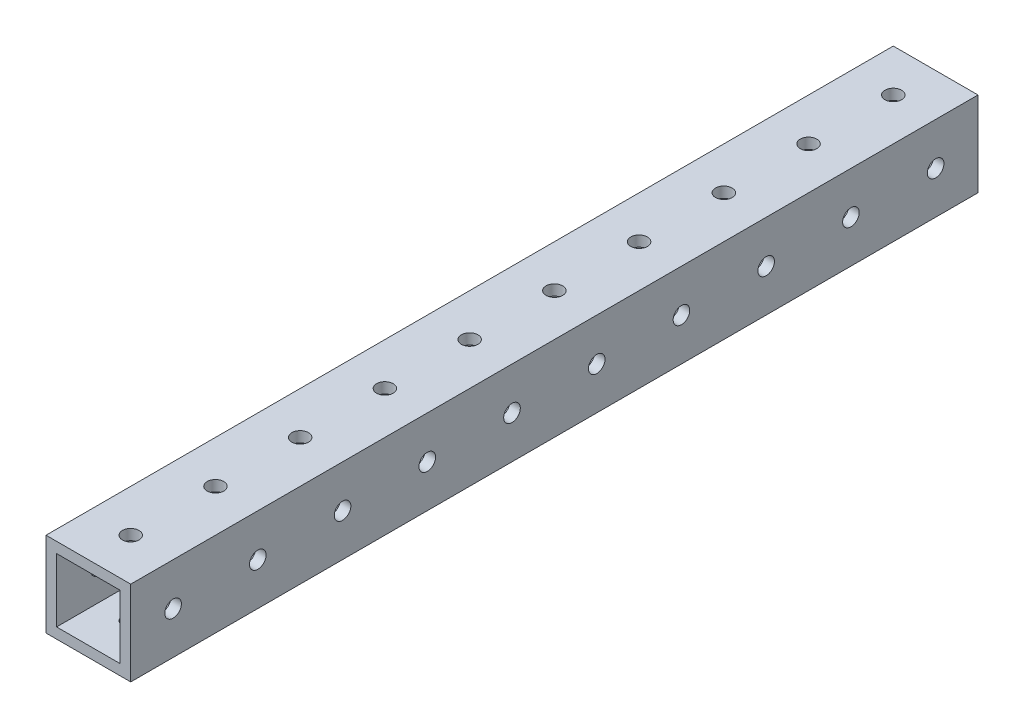
SolidWorks part; units mm, degrees
material "6061-T6 (SS)"
ref_plane "Front Plane" through (0, 0, 0) normal (0, 0, 1) x (1, 0, 0)
ref_plane "Top Plane" through (0, 0, 0) normal (0, 1, 0) x (1, 0, 0)
ref_plane "Right Plane" through (0, 0, 0) normal (1, 0, 0) x (0, 0, -1)
sketch "Sketch1" plane through (0, 0, 0) normal (0, 0, 1) x (1, 0, 0)
  line L1 (-12.7, -12.7) -> (12.7, -12.7)
  line L2 (-12.7, -12.7) -> (-12.7, 12.7)
  line L3 (-12.7, 12.7) -> (12.7, 12.7)
  line L4 (12.7, -12.7) -> (12.7, 12.7)
  line L5 (-12.7, -12.7) -> (12.7, 12.7) construction
  line L6 (-12.7, 12.7) -> (12.7, -12.7) construction
  point P0 (0, 0)
  dimension "D1" = 25.4
  dimension "D2" = 25.4
extrude "Boss-Extrude1" add sketch "Sketch1" along normal mid plane 254
shell "Shell1" thickness 3.175 removed face at (0, 0, -127) removed face at (0, 0, 127)
sketch "Sketch2" plane through (0, 12.7, 0) normal (0, 1, 0) x (1, 0, 0)
  line L0 (12.7, -127) -> (-12.7, -127) construction
  line L1 (12.7, -127) -> (12.7, 127) construction
  circle A0 centre (0, -114.3) radius 2.4892
  circle A1 centre (0, -88.9) radius 2.4892
  circle A2 centre (0, -63.5) radius 2.4892
  circle A3 centre (0, -38.1) radius 2.4892
  circle A4 centre (0, -12.7) radius 2.4892
  circle A5 centre (0, 12.7) radius 2.4892
  circle A6 centre (0, 38.1) radius 2.4892
  circle A7 centre (0, 63.5) radius 2.4892
  circle A8 centre (0, 88.9) radius 2.4892
  circle A9 centre (0, 114.3) radius 2.4892
  dimension "D1" = 4.9784
  dimension "D2" = 12.7
  dimension "D3" = 12.7
  dimension "D4" = 10
extrude "Cut-Extrude1" cut sketch "Sketch2" against normal through all
sketch "Sketch3" plane through (-12.7, 0, 0) normal (-1, 0, 0) x (0, 0, 1)
  line L0 (127, -12.7) -> (-127, -12.7) construction
  line L1 (127, 12.7) -> (127, -12.7) construction
  circle A0 centre (114.3, 0) radius 2.4892
  circle A1 centre (88.9, 0) radius 2.4892
  circle A2 centre (63.5, 0) radius 2.4892
  circle A3 centre (38.1, 0) radius 2.4892
  circle A4 centre (12.7, 0) radius 2.4892
  circle A5 centre (-12.7, 0) radius 2.4892
  circle A6 centre (-38.1, 0) radius 2.4892
  circle A7 centre (-63.5, 0) radius 2.4892
  circle A8 centre (-88.9, 0) radius 2.4892
  circle A9 centre (-114.3, 0) radius 2.4892
  dimension "D3" = 4.9784
  dimension "D1" = 12.7
  dimension "D2" = 12.7
  dimension "D4" = 10
extrude "Cut-Extrude2" cut sketch "Sketch3" against normal through all
